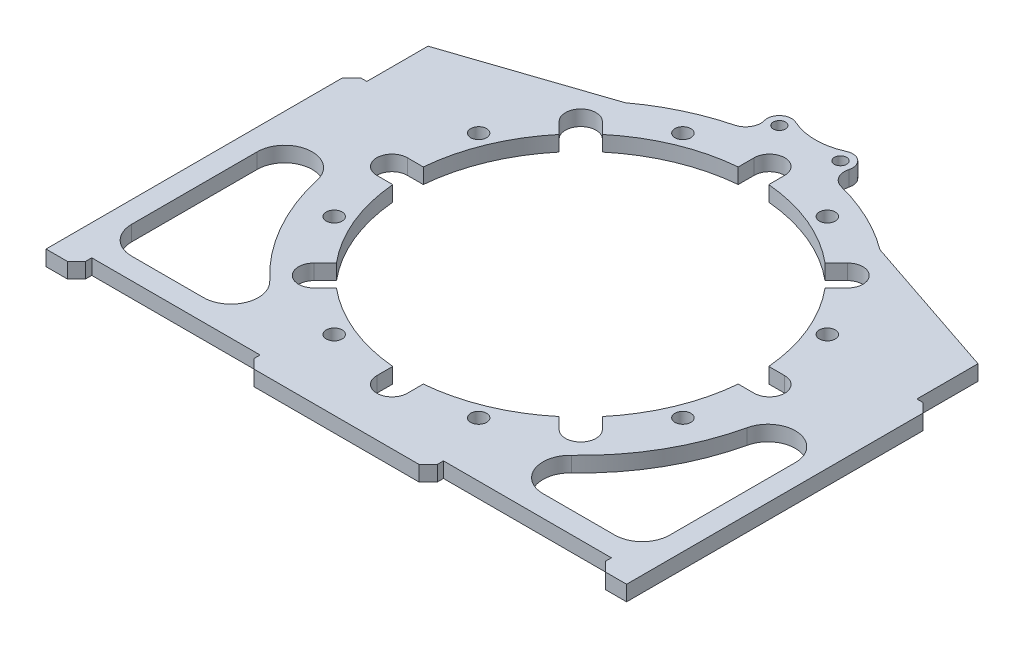
SolidWorks part; units mm, degrees
material "Stal węglowa"
ref_plane "Front" through (0, 0, 0) normal (0, 0, 1) x (1, 0, 0)
ref_plane "Top" through (0, 0, 0) normal (0, 1, 0) x (1, 0, 0)
ref_plane "Right" through (0, 0, 0) normal (1, 0, 0) x (0, 0, -1)
sketch "Szkic1" plane through (0, 0, 0) normal (0, 1, 0) x (1, 0, 0)
  line L118 (95, -79.9991) -> (95, 17)
  line L119 (-95, -80) -> (-95, 17)
  line L120 (-26.9346, -80) -> (27.0654, -80)
  line L121 (-29.9346, -74.9983) -> (-29.9346, -77)
  line L122 (30.0654, -77) -> (30.0654, -74.9991)
  line L123 (-85.0292, -74.999) -> (-29.9346, -74.9983)
  line L124 (30.0654, -74.9991) -> (85.0291, -74.9991)
  line L125 (85.0291, -76.9991) -> (85.0291, -74.9991)
  line L126 (-85.0292, -74.999) -> (-85.0292, -77)
  line L127 (-88.0292, -80) -> (-95, -80)
  line L128 (88.0291, -79.9991) -> (95, -79.9991)
  line L129 (90, 20) -> (92, 20)
  line L130 (90, 40) -> (90, 20)
  line L131 (-90, 20) -> (-90, 40)
  line L132 (-92, 20) -> (-90, 20)
  line L133 (-47.1994, -40.1283) -> (-43.5078, -36.4367)
  line L134 (-40.1283, -47.1994) -> (-36.4367, -43.5078)
  line L135 (47.1994, 40.1283) -> (43.5078, 36.4367)
  line L136 (40.1283, 47.1994) -> (36.4367, 43.5078)
  line L137 (5, 61.75) -> (5, 56.5293)
  line L138 (40.1283, -47.1994) -> (36.4367, -43.5078)
  line L139 (-61.75, 5) -> (-56.5293, 5)
  line L140 (61.75, -5) -> (56.5293, -5)
  line L141 (-5, -61.75) -> (-5, -56.5293)
  line L142 (-5, 61.75) -> (-5, 56.5293)
  line L143 (5, -61.75) -> (5, -56.5293)
  line L144 (-47.1994, 40.1283) -> (-43.5078, 36.4367)
  line L145 (-61.75, -5) -> (-56.5293, -5)
  line L146 (61.75, 5) -> (56.5293, 5)
  line L147 (-40.1283, 47.1994) -> (-36.4367, 43.5078)
  line L148 (47.1994, -40.1283) -> (43.5078, -36.4367)
  line L149 (90, 40) -> (41.6657, 56.2492)
  line L150 (-90, 40) -> (-41.6657, 56.2492)
  line L151 (55.6297, -67.999) -> (79.1309, -67.999)
  line L152 (88.1309, -58.999) -> (88.1309, -17.8884)
  line L153 (-55.4988, -67.999) -> (-79, -67.999)
  line L154 (-88, -58.999) -> (-88, -17.8884)
  line L155 (-29.9346, -77) -> (-26.9346, -80)
  line L156 (-88.0292, -80) -> (-85.0292, -77)
  line L157 (27.0654, -80) -> (30.0654, -77)
  line L158 (85.0291, -76.9991) -> (88.0291, -79.9991)
  line L159 (95, 17) -> (92, 20)
  line L160 (-95, 17) -> (-92, 20)
  arc A33 (36.4367, 43.5078) -> (5, 56.5293) centre (0, 0) ccw
  arc A34 (-5, 56.5293) -> (-36.4367, 43.5078) centre (0, 0) ccw
  arc A35 (-36.4367, -43.5078) -> (-5, -56.5293) centre (0, 0) ccw
  arc A36 (-47.1994, -40.1283) -> (-40.1283, -47.1994) centre (-43.6638, -43.6638) ccw
  arc A37 (-43.5078, 36.4367) -> (-56.5293, 5) centre (0, 0) ccw
  arc A38 (-56.5293, -5) -> (-43.5078, -36.4367) centre (0, 0) ccw
  arc A39 (5, -56.5293) -> (36.4367, -43.5078) centre (0, 0) ccw
  arc A40 (56.5293, 5) -> (43.5078, 36.4367) centre (0, 0) ccw
  circle A41 centre (-23.6307, -57.0496) radius 2.6
  arc A42 (5, 61.75) -> (-5, 61.75) centre (0, 61.75) ccw
  circle A43 centre (57.0496, -23.6307) radius 2.6
  circle A44 centre (57.0496, 23.6307) radius 2.6
  circle A45 centre (-57.0496, 23.6307) radius 2.6
  circle A46 centre (-57.0496, -23.6307) radius 2.6
  arc A47 (61.75, -5) -> (61.75, 5) centre (61.75, 0) ccw
  circle A48 centre (23.6307, 57.0496) radius 2.6
  arc A49 (47.1994, 40.1283) -> (40.1283, 47.1994) centre (43.6638, 43.6638) ccw
  arc A50 (40.1283, -47.1994) -> (47.1994, -40.1283) centre (43.6638, -43.6638) ccw
  arc A51 (-5, -61.75) -> (5, -61.75) centre (0, -61.75) ccw
  circle A52 centre (-23.6307, 57.0496) radius 2.6
  arc A53 (-61.75, 5) -> (-61.75, -5) centre (-61.75, 0) ccw
  arc A54 (-40.1283, 47.1994) -> (-47.1994, 40.1283) centre (-43.6638, 43.6638) ccw
  circle A55 centre (23.6307, -57.0496) radius 2.6
  arc A56 (43.5078, -36.4367) -> (56.5293, -5) centre (0, 0) ccw
  arc A57 (41.6657, 56.2492) -> (17.4383, 67.7931) centre (0, 0) ccw
  arc A58 (49.4631, -52.4436) -> (55.6297, -67.999) centre (55.6297, -58.999) ccw
  arc A59 (49.4631, -52.4436) -> (70.3531, -15.9008) centre (0.1309, 0) ccw
  arc A60 (79.1309, -67.999) -> (88.1309, -58.999) centre (79.1309, -58.999) ccw
  arc A61 (-88, -58.999) -> (-79, -67.999) centre (-79, -58.999) ccw
  arc A62 (-55.4988, -67.999) -> (-49.3323, -52.4436) centre (-55.4988, -58.999) ccw
  arc A63 (-70.2222, -15.9008) -> (-49.3323, -52.4436) centre (0, 0) ccw
  arc A64 (-70.2222, -15.9008) -> (-88, -17.8884) centre (-79, -17.8884) ccw
  arc A65 (88.1309, -17.8884) -> (70.3531, -15.9008) centre (79.1309, -17.8884) ccw
  arc A66 (-17.4383, 67.7931) -> (-13.8595, 73.9491) centre (-18.6838, 72.6355) ccw
  arc A67 (13.8595, 73.9491) -> (17.4383, 67.7931) centre (18.6838, 72.6355) ccw
  arc A68 (-17.4383, 67.7931) -> (-41.6657, 56.2492) centre (0, 0) ccw
  circle A69 centre (-10, 75) radius 2
  arc A70 (-8.3333, 78.6362) -> (-13.8595, 73.9491) centre (-10, 75) ccw
  arc A71 (-8.3333, 78.6362) -> (8.3333, 78.6362) centre (0, 96.8174) ccw
  arc A72 (13.8595, 73.9491) -> (8.3333, 78.6362) centre (10, 75) ccw
  circle A73 centre (10, 75) radius 2
extrude "Dodanie-wyciągnięcie1" add sketch "Szkic1" along normal blind 5
